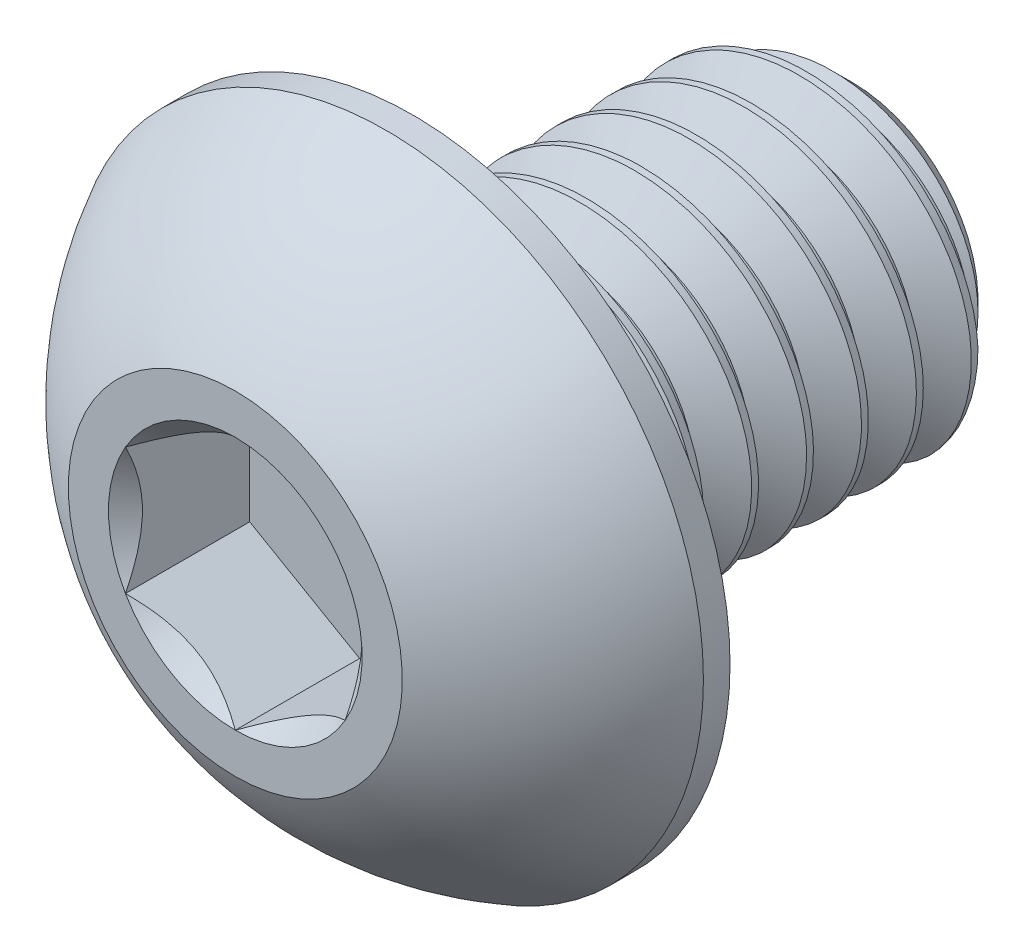
SolidWorks part; units mm, degrees
ref_plane "Front" through (0, 0, 0) normal (0, 0, 1) x (1, 0, 0)
ref_plane "Top" through (0, 0, 0) normal (0, 1, 0) x (1, 0, 0)
ref_plane "Right" through (0, 0, 0) normal (1, 0, 0) x (0, 0, -1)
sketch "Sketch1" plane through (0, 0, 0) normal (1, 0, 0) x (0, 0, -1)
  line L2 (2.5654, 2.413) -> (8.9154, 2.413)
  line L3 (8.9154, 2.413) -> (8.9154, 0)
  line L4 (8.9154, 0) -> (2.5654, 0)
  line L6 (2.1806, 4.5847) -> (2.5654, 4.5847) construction
  line L7 (8.9154, 2.413) -> (8.9154, -2.413) construction
  line L8 (0, 0) -> (2.5654, 0) construction
  line L9 (2.5654, 4.5847) -> (2.5654, -4.5847) construction
  line L11 (2.5654, 2.413) -> (2.5654, 0)
  line L13 (0, 1.5875) -> (0, -1.5875) construction
  line L14 (0, 1.5875) -> (0, 2.413) construction
  arc A3 (0, 2.413) -> (2.1806, 4.5847) centre (4.5749, 0) cw construction
  dimension "D1" = 0.3848
revolve "Revolve1" add sketch "Sketch1" angle 360 mid plane about L4
sketch "Sketch3" plane through (0, 0, -8.9154) normal (0, 0, -1) x (-1, 0, 0)
  circle A0 centre (0, 0) radius 2.413
curve "Helix/Spiral1" pitch 0.7937 height 7.1437 turns 9
sketch "Sketch2" plane through (0, 0, 0) normal (1, 0, 0) x (0, 0, -1)
  line L0 (8.9154, 2.413) -> (9.6099, 2.413)
  line L1 (9.6099, 2.413) -> (9.3123, 1.8974)
  line L2 (9.3123, 1.8974) -> (9.2131, 1.8974)
  line L3 (9.2131, 1.8974) -> (8.9154, 2.413)
  line L4 (9.0642, 2.1552) -> (9.4611, 2.1552) construction
  dimension "D1" = 60
  dimension "D2" = 0.0992
  dimension "D3" = 0.3969
chamfer "Chamfer1" distance 0.5953 angle 45 1 edges at (0, 2.413, -8.9154)
sweep "Cut-Sweep1" cut profiles "Sketch2" path "Helix/Spiral1"
sketch "Sketch7" plane through (0, 0, 0) normal (1, 0, 0) x (0, 0, -1)
  line L6 (2.1806, 4.5847) -> (2.5654, 4.5847) construction
  line L8 (0, 0) -> (2.5654, 0) construction
  line L11 (2.5654, 4.5847) -> (2.5654, -4.5847) construction
  line L12 (2.1806, 4.5847) -> (2.5654, 4.5847)
  line L13 (0, 0) -> (2.5654, 0)
  line L14 (0, 1.5875) -> (0, -1.5875) construction
  line L15 (2.5654, 4.5847) -> (2.5654, 0)
  line L16 (0, 2.413) -> (0, 0)
  arc A2 (2.1806, 4.5847) -> (0, 2.413) centre (4.5749, 0) ccw construction
  arc A3 (2.1806, 4.5847) -> (0, 2.413) centre (4.5749, 0) ccw
revolve "Revolve2" add sketch "Sketch7" angle 360 mid plane about L13
sketch "Sketch5" plane through (0, 0, 0) normal (0, 0, 1) x (1, 0, 0)
  line L1 (1.5875, -0.9165) -> (1.5875, 0.9165)
  line L2 (1.5875, 0.9165) -> (0, 1.8331)
  line L3 (0, 1.8331) -> (-1.5875, 0.9165)
  line L4 (-1.5875, 0.9165) -> (-1.5875, -0.9165)
  line L5 (-1.5875, -0.9165) -> (0, -1.8331)
  line L6 (0, -1.8331) -> (1.5875, -0.9165)
  circle A0 centre (0, 0) radius 1.5875 construction
extrude "Cut-Extrude2" cut sketch "Sketch5" against normal blind 1.7958
sketch "Sketch6" plane through (0, 0, 0) normal (0, 0, 1) x (1, 0, 0)
  circle A0 centre (0, 0) radius 1.8331
extrude "Cut-Extrude3" cut sketch "Sketch6" against normal blind 1.7958 draft 45
sketch "Sketch9" [suppressed] plane through (0, 0, -2.5654) normal (0, 0, 1) x (1, 0, 0)
  circle A2 centre (0, 0) radius 2.413
extrude "Boss-Extrude2" [suppressed] add sketch "Sketch9" against normal offset from surface (9.525 mm away) 31.75
sketch "Sketch10" plane through (0, 0, 0) normal (1, 0, 0) x (0, 0, -1)
  line L0 (8.9154, 2.413) -> (8.9154, -2.413) construction
  point P0 (7.7248, -2.413)
  dimension "D1" = 1.1906
equation "\"D3@Helix/Spiral1\" = \"Lg@Sketch1\" + \"D4@Helix/Spiral1\""
equation "\"D2@Sketch2\" = \"D4@Helix/Spiral1\" * .125"
equation "\"D3@Sketch2\" = \"D4@Helix/Spiral1\" * .5"
equation "\"D1@Chamfer1\" = \"D4@Helix/Spiral1\" * .75"
equation "\"D1@Cut-Extrude2\" = \"Head Ht@Sketch1\" * .7"
equation "\"D1@Sketch1\" = \"Head Ht@Sketch1\" * .15"
equation "\"D1@Sketch10\" = \"D4@Helix/Spiral1\" * 1.5"
equation "\"D1@Cut-Extrude3\" = \"D1@Cut-Extrude2\""
